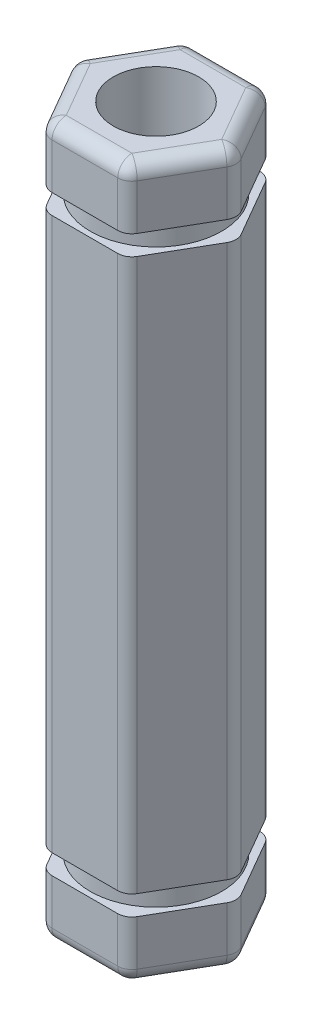
SolidWorks part; units mm, degrees
material "Brass"
ref_plane "Front Plane" through (0, 0, 0) normal (0, 0, 1) x (1, 0, 0)
ref_plane "Top Plane" through (0, 0, 0) normal (0, 1, 0) x (1, 0, 0)
ref_plane "Right Plane" through (0, 0, 0) normal (1, 0, 0) x (0, 0, -1)
sketch "Sketch1" plane through (0, 0, 0) normal (0, 1, 0) x (1, 0, 0)
  line L1 (-1.4434, 2.5) -> (-2.8868, 0)
  line L2 (-2.8868, 0) -> (-1.4434, -2.5)
  line L3 (-1.4434, -2.5) -> (1.4434, -2.5)
  line L4 (1.4434, -2.5) -> (2.8868, 0)
  line L5 (2.8868, 0) -> (1.4434, 2.5)
  line L6 (1.4434, 2.5) -> (-1.4434, 2.5)
  circle A0 centre (0, 0) radius 2.5 construction
  circle A1 centre (0, 0) radius 1.5
  dimension "D2" = 3
  dimension "D1" = 5
extrude "Boss-Extrude1" add sketch "Sketch1" along normal blind 25
fillet "Fillet1" radius 0.5 18 edges at (0, 25, -2.5) (0, 0, -2.5) (2.1651, 25, -1.25) (1.4434, 12.5, -2.5) (2.1651, 0, -1.25) (2.1651, 25, 1.25) (2.8868, 12.5, 0) (2.1651, 0, 1.25) (-2.1651, 25, 1.25) (-2.1651, 0, 1.25) (-1.4434, 12.5, -2.5) (-2.1651, 25, -1.25) (-2.8868, 12.5, 0) (-2.1651, 0, -1.25) (-1.4434, 12.5, 2.5) (0, 25, 2.5) (1.4434, 12.5, 2.5) (0, 0, 2.5)
sketch "Sketch2" plane through (0, 0, 0) normal (0, 0, 1) x (1, 0, 0)
  line L0 (0, 25) -> (0, 0) construction
  line L1 (-1.1547, 25) -> (1.1547, 25) construction
  line L2 (2.8094, 0.5) -> (2.8094, 24.5) construction
  line L3 (-2.8094, 2.8) -> (2.8094, 2.8)
  line L4 (-2.8094, 2.8) -> (-2.8094, 22.2)
  line L5 (-2.8094, 22.2) -> (2.8094, 22.2)
  line L6 (2.8094, 2.8) -> (2.8094, 22.2)
  line L7 (-2.8094, 2.8) -> (2.8094, 22.2) construction
  line L8 (-2.8094, 22.2) -> (2.8094, 2.8) construction
  line L10 (2.8094, 22.2) -> (2.3094, 22.2)
  line L11 (2.8094, 22.2) -> (2.8094, 22.9)
  line L12 (2.8094, 22.9) -> (2.3094, 22.9)
  line L13 (2.3094, 22.2) -> (2.3094, 22.9)
  line L14 (2.8094, 2.8) -> (2.3094, 2.8)
  line L15 (2.8094, 2.8) -> (2.8094, 2.1)
  line L16 (2.8094, 2.1) -> (2.3094, 2.1)
  line L17 (2.3094, 2.8) -> (2.3094, 2.1)
  point P5 (0, 12.5)
  dimension "D1" = 19.4
  dimension "D2" = 0.7
  dimension "D3" = 0.5
revolve "Cut-Revolve1" cut sketch "Sketch2" angle 360 about L0
